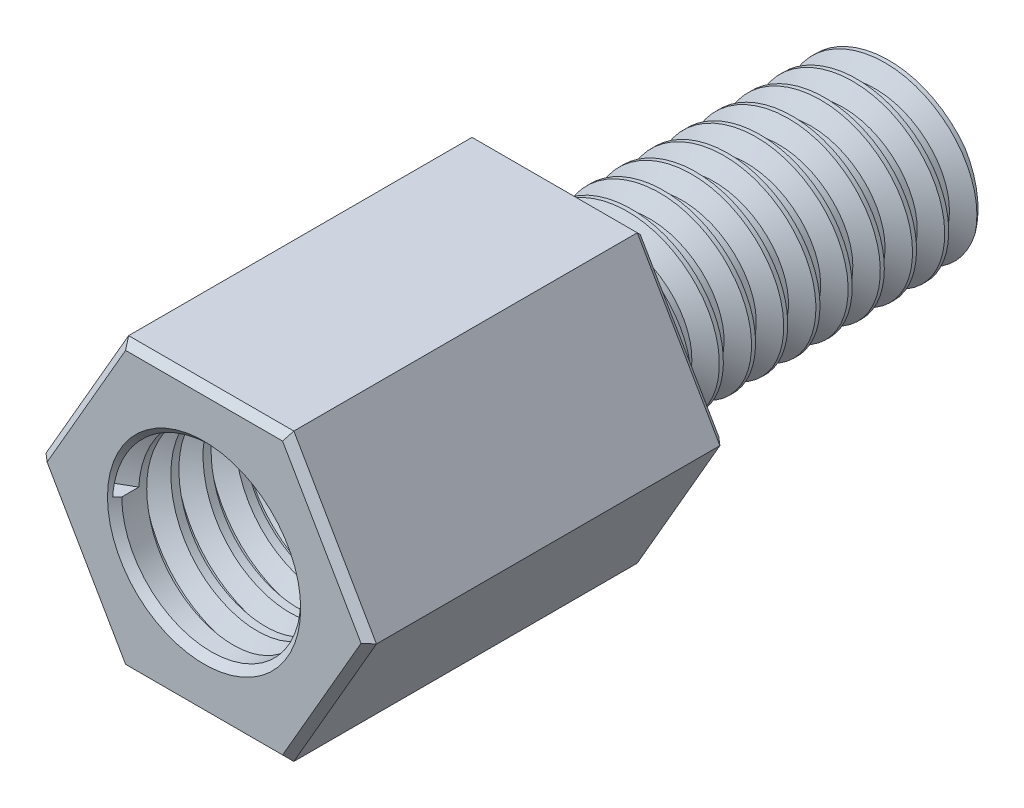
SolidWorks part; units mm, degrees
ref_plane "Front" through (0, 0, 0) normal (0, 0, 1) x (1, 0, 0)
ref_plane "Top" through (0, 0, 0) normal (0, 1, 0) x (1, 0, 0)
ref_plane "Right" through (0, 0, 0) normal (1, 0, 0) x (0, 0, -1)
sketch "Sketch1" plane through (0, 0, 0) normal (0, 0, 1) x (1, 0, 0)
  line L1 (2.3094, 0) -> (1.1547, 2)
  line L2 (1.1547, 2) -> (-1.1547, 2)
  line L3 (-1.1547, 2) -> (-2.3094, 0)
  line L4 (-2.3094, 0) -> (-1.1547, -2)
  line L5 (-1.1547, -2) -> (1.1547, -2)
  line L6 (1.1547, -2) -> (2.3094, 0)
  circle A0 centre (0, 0) radius 2 construction
  dimension "D1" = 4
extrude "Boss-Extrude1" add sketch "Sketch1" along normal blind 5
sketch "Sketch2" plane through (0, 0, 5) normal (0, 0, 1) x (1, 0, 0)
  circle A0 centre (0, 0) radius 1.25
  dimension "D1" = 2.5
extrude "Cut-Extrude1" cut sketch "Sketch2" against normal blind 4
thread "Thread1" pitch 0.45 method cut profile "Thread Profile1" start angle 0, offset 0, length 4, pitch 0.45, diameter 2.5
ref_plane "Plane1" through (-1.25, 0, 5) normal (0, -1, 0) x (-1, 0, 0)
sketch "Thread Profile1" plane through (-1.25, 0, 5) normal (0, -1, 0) x (-1, 0, 0)
  line L0 (0, 0) -> (0, 0.45) construction
  line L1 (0, 0) -> (0.2436, 0.1406)
  line L2 (0.2436, 0.1406) -> (0.2436, 0.1969)
  line L3 (0.2436, 0.1969) -> (0, 0.3375)
  line L4 (0.2436, 0.1687) -> (0, 0.1687) construction
  line L11 (0, 0) -> (0, 0.3375)
  point P2 (0, 0)
  dimension "Pitch" = 0.45
  dimension "Profile_Angle" = 60
  dimension "Profile_Land" = 0.0562
  dimension "Profile_Height" = 0.2436
chamfer "Chamfer1" distance 0.1 angle 45 7 edges at (0, -2, 5) (-1.7321, -1, 5) (-1.7321, 1, 5) (0, 2, 5) (1.7321, 1, 5) (1.7321, -1, 5) (1.25, 0, 5)
chamfer "Chamfer2" distance 0.1 angle 45 6 edges at (1.7321, 1, 0) (0, 2, 0) (-1.7321, 1, 0) (-1.7321, -1, 0) (0, -2, 0) (1.7321, -1, 0)
sketch "Sketch6" plane through (0, 0, 0) normal (0, 0, -1) x (-1, 0, 0)
  circle A0 centre (0, 0) radius 1.25
  dimension "D1" = 2.5
extrude "Boss-Extrude2" add sketch "Sketch6" along normal blind 5
thread "Thread2" pitch 0.45 method cut profile "Thread Profile2" start angle 0, offset 0, length 5, pitch 0.45, diameter 2.5
ref_plane "Plane2" through (1.25, 0, -5) normal (0, -1, 0) x (1, 0, 0)
sketch "Thread Profile2" plane through (1.25, 0, -5) normal (0, -1, 0) x (1, 0, 0)
  line L0 (0, 0) -> (0, 0.45) construction
  line L11 (0, 0) -> (0, 0.3937)
  line L12 (0, 0.3937) -> (-0.2436, 0.2531)
  line L13 (-0.2436, 0.2531) -> (-0.2436, 0.1406)
  line L15 (-0.2436, 0.1406) -> (0, 0)
  line L17 (-0.2436, 0.1969) -> (0, 0.1969) construction
  point P2 (0, 0)
  dimension "Pitch" = 0.45
  dimension "Profile_Angle" = 60
  dimension "Profile_Land" = 0.1125
  dimension "Profile_Height" = 0.2436
ref_axis "Axis1" through (0, 0, -10) along (0, 0, 1)
sketch "Sketch7" plane through (0, 0, 0) normal (0, 1, 0) x (1, 0, 0)
  line L0 (-0.3617, 5) -> (-1.4508, 4.4699)
  line L1 (1.25, 5) -> (-1.25, 5) construction
  line L2 (-1.4508, 4.4699) -> (-1.4508, 5.2733)
  line L3 (-1.4508, 5.2733) -> (-0.3617, 5.2733)
  line L4 (-0.3617, 5.2733) -> (-0.3617, 5)
revolve "Cut-Revolve1" cut sketch "Sketch7" angle 360 about axis through (0, 0, -10) along (0, 0, 1)
